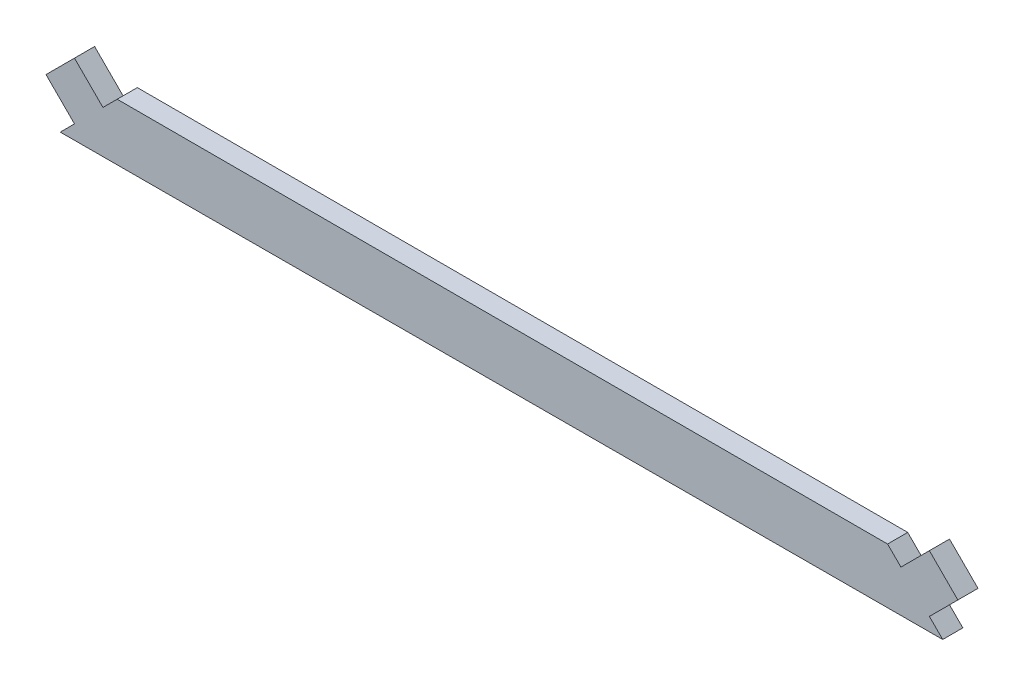
SolidWorks part; units mm, degrees
ref_plane "Front Plane" through (0, 0, 0) normal (0, 0, 1) x (1, 0, 0)
ref_plane "Top Plane" through (0, 0, 0) normal (0, 1, 0) x (1, 0, 0)
ref_plane "Right Plane" through (0, 0, 0) normal (1, 0, 0) x (0, 0, -1)
sketch "Sketch1" plane through (0, 0, 0) normal (0, 0, 1) x (1, 0, 0)
  line L0 (-139.4438, -165.8849) -> (138.8703, -165.3114)
  line L1 (0, -26.4411) -> (139.4438, -165.8849) construction
  line L2 (138.8703, -165.3114) -> (121.4833, -147.9244)
  line L3 (121.4833, -147.9244) -> (-121.4833, -147.9244)
  line L4 (-139.4438, -165.8849) -> (0, -26.4411) construction
  line L5 (-121.4833, -147.9244) -> (-139.4438, -165.8849)
  arc A0 (138.8703, -165.3114) -> (-138.8703, -165.3114) centre (0, 0) ccw construction
  dimension "D1" = 25.4
extrude "Boss-Extrude1" add sketch "Sketch1" along normal mid plane 6.35
sketch "Sketch2" plane through (0, 0, -3.175) normal (0, 0, -1) x (-1, 0, 0)
  line L0 (-130.1768, -156.6179) -> (-127.0422, -159.7525) construction
  line L1 (-138.8703, -165.3114) -> (-121.4833, -147.9244) construction
  line L2 (-125.6867, -152.1278) -> (-134.6669, -143.1475)
  line L3 (-134.6669, -143.1475) -> (-143.6472, -152.1278)
  line L4 (-143.6472, -152.1278) -> (-134.6669, -161.108)
  line L8 (-121.4833, -147.9244) -> (-125.6867, -152.1278)
  line L12 (139.4438, -165.8849) -> (121.4833, -147.9244)
  line L13 (121.4833, -147.9244) -> (-121.4833, -147.9244)
  line L14 (-121.4833, -147.9244) -> (-138.8703, -165.3114)
  line L15 (-138.8703, -165.3114) -> (139.4438, -165.8849)
  line L16 (139.4438, -165.8849) -> (121.4833, -147.9244)
  line L17 (121.4833, -147.9244) -> (-121.4833, -147.9244)
  line L18 (-134.6669, -161.108) -> (-138.8703, -165.3114)
  line L19 (-138.8703, -165.3114) -> (139.4438, -165.8849)
  dimension "D1" = 12.7
  dimension "D2" = 12.7
  dimension "D3" = 0
extrude "Boss-Extrude2" add sketch "Sketch2" against normal up to surface (6.35 mm away) up to face at (-0.1434, -156.7613, 3.175)
sketch "Sketch3" plane through (0, 0, -3.175) normal (0, 0, -1) x (-1, 0, 0)
  line L0 (130.4636, -156.9046) -> (137.1973, -150.1709) construction
  line L1 (121.4833, -147.9244) -> (139.4438, -165.8849) construction
  line L2 (125.9734, -152.4145) -> (134.9537, -143.4343)
  line L3 (134.9537, -143.4343) -> (143.9339, -152.4145)
  line L4 (143.9339, -152.4145) -> (134.9537, -161.3948)
  line L13 (139.4438, -165.8849) -> (121.4833, -147.9244)
  line L14 (121.4833, -147.9244) -> (-121.4833, -147.9244)
  line L15 (-121.4833, -147.9244) -> (-125.6867, -152.1278)
  line L16 (-125.6867, -152.1278) -> (-134.6669, -143.1475)
  line L17 (-134.6669, -143.1475) -> (-143.6472, -152.1278)
  line L18 (-143.6472, -152.1278) -> (-134.6669, -161.108)
  line L19 (-134.6669, -161.108) -> (-138.8703, -165.3114)
  line L20 (-138.8703, -165.3114) -> (139.4438, -165.8849)
  line L21 (134.9537, -161.3948) -> (125.9734, -152.4145)
  dimension "D1" = 12.7
  dimension "D2" = 12.7
  dimension "D3" = 0
extrude "Boss-Extrude4" add sketch "Sketch3" against normal blind 6.35
